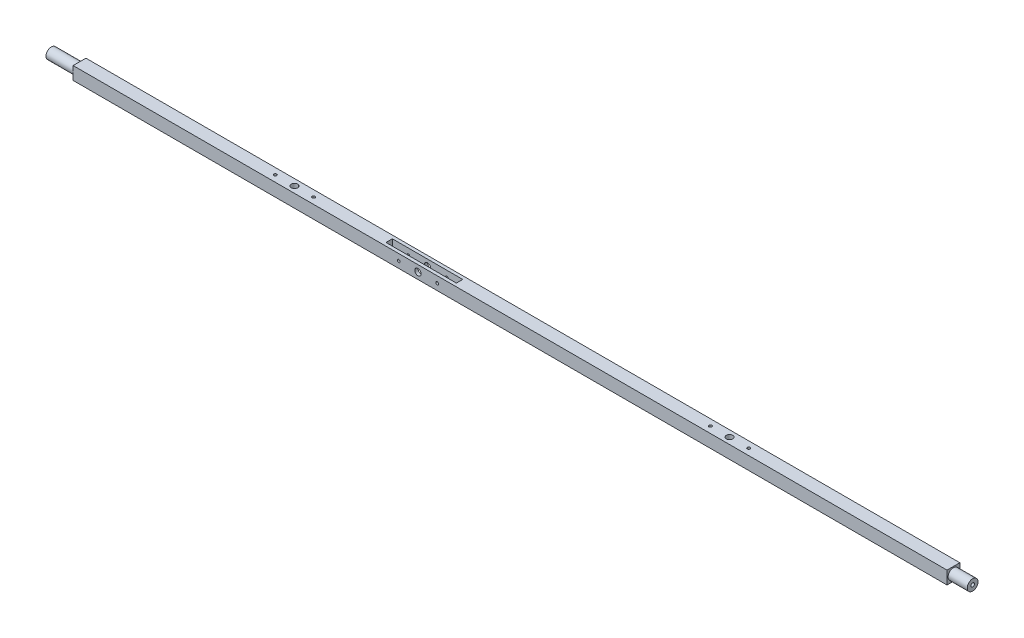
SolidWorks part; units mm, degrees
material "6061-T6 (SS)"
ref_plane "Front Plane" through (0, 0, 0) normal (0, 0, 1) x (1, 0, 0)
ref_plane "Top Plane" through (0, 0, 0) normal (0, 1, 0) x (1, 0, 0)
ref_plane "Right Plane" through (0, 0, 0) normal (1, 0, 0) x (0, 0, -1)
sketch "Sketch1" plane through (0, 0, 0) normal (1, 0, 0) x (0, 0, -1)
  line L1 (-6.35, -6.4107) -> (6.35, -6.4107)
  line L2 (-6.35, -6.4107) -> (-6.35, 6.4107)
  line L3 (-6.35, 6.4107) -> (6.35, 6.4107)
  line L4 (6.35, -6.4107) -> (6.35, 6.4107)
  line L5 (-6.35, -6.4107) -> (6.35, 6.4107) construction
  line L6 (-6.35, 6.4107) -> (6.35, -6.4107) construction
  point P0 (0, 0)
  dimension "D1" = 12.7
  dimension "D2" = 12.8213
extrude "Length" add sketch "Sketch1" along normal mid plane 914.4
ref_plane "Top" through (457.2, 0, 0) normal (1, 0, 0) x (0, 0, -1)
sketch "Sketch2" plane through (457.2, 0, 0) normal (1, 0, 0) x (0, 0, -1)
  line L5 (-3.7537, -3.7896) -> (2.2344, 2.2557) construction
  line L6 (-3.7537, 3.7896) -> (3.7537, -3.7896) construction
  line L7 (-6.35, -6.4107) -> (6.35, -6.4107)
  line L8 (-6.35, -6.4107) -> (-6.35, 6.4107)
  line L9 (-6.35, 6.4107) -> (6.35, 6.4107)
  line L10 (6.35, -6.4107) -> (6.35, 6.4107)
  line L11 (-6.35, -6.4107) -> (6.35, 6.4107) construction
  line L12 (-6.35, 6.4107) -> (6.35, -6.4107) construction
  circle A0 centre (0, 0) radius 5.334
  point P0 (0, 0)
  dimension "D1" = 10.668
extrude "Round Cut 1" cut sketch "Sketch2" against normal blind 19.05 contours L7 L10 L9 L8 A0 region at (457.2, 0, 6.1695)
ref_plane "Bottom Plane" through (-457.2, 0, 0) normal (-1, 0, 0) x (0, 0, 1)
sketch "Sketch3" plane through (-457.2, 0, 0) normal (-1, 0, 0) x (0, 0, 1)
  line L1 (-6.35, -6.4107) -> (6.35, -6.4107)
  line L2 (-6.35, -6.4107) -> (-6.35, 6.4107)
  line L3 (-6.35, 6.4107) -> (6.35, 6.4107)
  line L4 (6.35, -6.4107) -> (6.35, 6.4107)
  line L5 (-6.35, -6.4107) -> (6.35, 6.4107) construction
  line L6 (-6.35, 6.4107) -> (6.35, -6.4107) construction
  circle A0 centre (0, 0) radius 5.334
  point P0 (0, 0)
  dimension "D1" = 10.668
extrude "Round Cut 2" cut sketch "Sketch3" against normal blind 27.94 contours L1 L4 L3 L2 A0 | L2 L1 L4 L3 | A0 region at (-457.2, 0, -6.1695)
ref_plane "Plane13" through (0, -6.4107, 0) normal (0, -1, 0) x (-1, 0, 0)
sketch "Sketch9" plane through (0, -6.4107, 0) normal (0, -1, 0) x (-1, 0, 0)
  line L0 (-438.15, 6.35) -> (429.26, 6.35) construction
  line L1 (-330.2, 6.35) -> (-279.4, 6.35)
  line L2 (-330.2, 6.35) -> (-330.2, -6.35)
  line L3 (-330.2, -6.35) -> (-279.4, -6.35)
  line L4 (-279.4, 6.35) -> (-279.4, -6.35)
  line L5 (-438.15, -6.35) -> (429.26, -6.35) construction
  line L6 (-457.2, 6.985) -> (-457.2, -6.985) construction
  dimension "D1" = 50.8
  dimension "D2" = 127
sketch "Sketch10" plane through (0, -6.4107, 0) normal (0, -1, 0) x (-1, 0, 0)
  line L0 (457.2, -5.334) -> (457.2, 5.334) construction
  line L1 (101.6, -4.7642) -> (406.4, -4.7642)
  line L2 (101.6, -4.7642) -> (101.6, 4.6338)
  line L3 (101.6, 4.6338) -> (406.4, 4.6338)
  line L4 (406.4, -4.7642) -> (406.4, 4.6338)
  line L5 (101.6, -4.7642) -> (406.4, 4.6338) construction
  line L6 (101.6, 4.6338) -> (406.4, -4.7642) construction
  point P0 (254, -0.0652)
  dimension "D1" = 9.398
  dimension "D2" = 304.8
  dimension "D3" = 203.2
extrude "Cut-Extrude2" [suppressed] cut sketch "Sketch10" against normal blind 7.5438
ref_plane "Plane14" through (0, 0, 6.35) normal (0, 0, 1) x (1, 0, 0)
sketch "Sketch11" [suppressed] plane through (0, 0, 6.35) normal (0, 0, 1) x (1, 0, 0)
  line L0 (-50.8, 1.1331) -> (-355.6, 1.1331) construction
  line L1 (-355.6, 1.1331) -> (-355.6, -6.4107) construction
  line L2 (-349.25, -2.6769) -> (-63.4679, -2.6769) construction
  circle A0 centre (-349.25, -2.6769) radius 1.2573
  circle A1 centre (-336.55, -2.6769) radius 1.2573
  circle A2 centre (-323.85, -2.6769) radius 1.2573
  circle A3 centre (-311.15, -2.6769) radius 1.2573
  circle A4 centre (-298.45, -2.6769) radius 1.2573
  circle A5 centre (-285.75, -2.6769) radius 1.2573
  circle A6 centre (-273.05, -2.6769) radius 1.2573
  circle A7 centre (-260.35, -2.6769) radius 1.2573
  circle A8 centre (-247.65, -2.6769) radius 1.2573
  circle A9 centre (-234.95, -2.6769) radius 1.2573
  circle A10 centre (-222.25, -2.6769) radius 1.2573
  circle A11 centre (-209.55, -2.6769) radius 1.2573
  circle A12 centre (-196.85, -2.6769) radius 1.2573
  circle A13 centre (-184.15, -2.6769) radius 1.2573
  circle A14 centre (-171.45, -2.6769) radius 1.2573
  circle A15 centre (-158.75, -2.6769) radius 1.2573
  circle A16 centre (-146.05, -2.6769) radius 1.2573
  circle A17 centre (-133.35, -2.6769) radius 1.2573
  circle A18 centre (-120.65, -2.6769) radius 1.2573
  circle A19 centre (-107.95, -2.6769) radius 1.2573
  circle A20 centre (-95.25, -2.6769) radius 1.2573
  circle A21 centre (-82.55, -2.6769) radius 1.2573
  circle A22 centre (-69.85, -2.6769) radius 1.2573
  circle A23 centre (-57.15, -2.6769) radius 1.2573
  dimension "D1" = 2.5146
  dimension "D2" = 3.81
  dimension "D3" = 24
  dimension "25" = 6.35
extrude "Cut-Extrude3" [suppressed] cut sketch "Sketch11" against normal through all
sketch "Sketch12" plane through (0, -6.4107, 0) normal (0, -1, 0) x (-1, 0, 0)
  line L1 (0, 3.175) -> (-38.1, 3.175)
  line L2 (0, 3.175) -> (0, -3.175)
  line L3 (0, -3.175) -> (-38.1, -3.175)
  line L4 (-38.1, 3.175) -> (-38.1, -3.175)
  dimension "D1" = 38.1
  dimension "D2" = 6.35
  dimension "D3" = 3.175
  dimension "D4" = 0
extrude "Cut-Extrude4" [suppressed] cut sketch "Sketch12" against normal blind 6.35
sketch "Sketch13" [suppressed] plane through (0, 0, 6.35) normal (0, 0, 1) x (1, 0, 0)
  line L0 (0, -0.0607) -> (0, -6.4107) construction
  line L1 (378.46, -6.4107) -> (-378.46, -6.4107) construction
  circle A0 centre (5.08, -3.2357) radius 1.2573
  circle A1 centre (13.97, -3.2357) radius 1.2573
  circle A2 centre (22.86, -3.2357) radius 1.2573
  circle A3 centre (31.75, -3.2357) radius 1.2573
  dimension "D1" = 2.5146
  dimension "D3" = 5.08
  dimension "D4" = 3.175
  dimension "D2" = 4
extrude "Cut-Extrude5" [suppressed] cut sketch "Sketch13" against normal through all
sketch "Sketch14" plane through (457.2, 0, 0) normal (1, 0, 0) x (0, 0, -1)
  circle A0 centre (0, 0) radius 1.7526
  dimension "D1" = 3.5052
extrude "Cut-Extrude6" cut sketch "Sketch14" against normal blind 12.7
sketch "Sketch15" plane through (-457.2, 0, 0) normal (-1, 0, 0) x (0, 0, 1)
  circle A0 centre (0, 0) radius 1.7526
  dimension "D1" = 3.5052
extrude "Cut-Extrude7" cut sketch "Sketch15" against normal blind 19.05
ref_plane "Plane15" through (0, 6.4107, 0) normal (0, 1, 0) x (1, 0, 0)
sketch "Bottom Washer" plane through (0, 6.4107, 0) normal (0, 1, 0) x (1, 0, 0)
  line L1 (-457.2, 5.334) -> (-457.2, -5.334) construction
  circle A1 centre (-196.85, 0) radius 1.4224
  circle A2 centre (-234.95, 0) radius 1.4224
  point P2 (-457.2, 1.3557)
  dimension "D4" = 2.8448
  dimension "D5" = 2.8448
  dimension "D1" = 222.25
  dimension "D2" = 38.1
extrude "Bottom washer bolts" cut sketch "Bottom Washer" against normal blind 10.922 contours A1 | A2 region at (-196.85, 6.4107, 0) region at (-234.95, 6.4107, 0)
sketch "Sketch18" plane through (0, 6.4107, 0) normal (0, 1, 0) x (1, 0, 0)
  line L0 (-457.2, 5.334) -> (-457.2, -5.334) construction
  circle A0 centre (-215.9, 0) radius 3.175
  dimension "D1" = 6.35
  dimension "D2" = 241.3
extrude "Bottom Washer Center Bolt" cut sketch "Sketch18" against normal up to next
sketch "Sketch17" plane through (0, 6.4107, 0) normal (0, 1, 0) x (1, 0, 0)
  line L0 (457.2, -5.334) -> (457.2, 5.334) construction
  circle A0 centre (215.9, 0) radius 3.175
  dimension "D1" = 6.35
  dimension "D2" = 241.3
extrude "Top Washer Center Bolt" cut sketch "Sketch17" against normal up to next
sketch "Sketch16" plane through (0, 6.4107, 0) normal (0, 1, 0) x (1, 0, 0)
  line L0 (457.2, -5.334) -> (457.2, 5.334) construction
  circle A1 centre (234.95, 0) radius 1.4224
  circle A2 centre (196.85, 0) radius 1.4224
  dimension "D1" = 38.1
  dimension "D3" = 2.8448
  dimension "D4" = 2.8448
  dimension "D2" = 222.25
extrude "Top Washer" cut sketch "Sketch16" against normal blind 10.922
ref_plane "Plane16" through (0, -6.4107, 0) normal (0, -1, 0) x (-1, 0, 0)
sketch "Sketch19" plane through (0, -6.4107, 0) normal (0, -1, 0) x (-1, 0, 0)
  line L0 (-438.15, 6.35) -> (429.26, 6.35) construction
  line L1 (52.0606, 3.175) -> (121.9106, 3.175)
  line L2 (52.0606, 3.175) -> (52.0606, -3.175)
  line L3 (52.0606, -3.175) -> (121.9106, -3.175)
  line L4 (121.9106, 3.175) -> (121.9106, -3.175)
  line L5 (429.26, 6.35) -> (429.26, -6.35) construction
  dimension "D1" = 6.35
  dimension "D2" = 3.175
  dimension "D3" = 69.85
  dimension "D4" = 307.3494
extrude "Cut-Extrude8" cut sketch "Sketch19" against normal through all
ref_plane "Plane17" through (0, 0, 6.35) normal (0, 0, 1) x (1, 0, 0)
sketch "Sketch20" plane through (0, 0, 6.35) normal (0, 0, 1) x (1, 0, 0)
  line L0 (-86.9856, 6.4107) -> (-86.9856, -6.4107) construction
  line L1 (-52.0606, 6.4107) -> (-52.0606, -6.4107) construction
  line L3 (-121.9106, 0) -> (-52.0606, 0) construction
  line L6 (-121.9106, -6.4107) -> (-52.0606, -6.4107)
  line L7 (-121.9106, 6.4107) -> (-121.9106, -6.4107)
  line L8 (-52.0606, 6.4107) -> (-121.9106, 6.4107)
  line L9 (-52.0606, -6.4107) -> (-52.0606, 6.4107)
  line L10 (-121.9106, -6.4107) -> (-52.0606, -6.4107) construction
  line L11 (-121.9106, 6.4107) -> (-121.9106, -6.4107) construction
  line L12 (-52.0606, 6.4107) -> (-121.9106, 6.4107) construction
  line L13 (-52.0606, -6.4107) -> (-52.0606, 6.4107) construction
  circle A0 centre (-106.0356, 0) radius 1.397
  circle A1 centre (-86.9856, 0) radius 3.175
  circle A2 centre (-67.9356, 0) radius 1.397
  point P18 (0, 0)
  point P19 (0, 0)
  dimension "D1" = 2.794
  dimension "D2" = 6.35
  dimension "D3" = 2.794
  dimension "D4" = 15.875
  dimension "D5" = 19.05
  dimension "D6" = 19.05
  dimension "D7" = 0
extrude "Cut-Extrude9" cut sketch "Sketch20" against normal through all
equation "\"Diameter\"= .420"
equation "\"Round Cut Depth Top\"= .75"
equation "\"Stringer Length\"=36"
equation "\"D1@Sketch3\"= \"Diameter\""
equation "\"D1@Sketch2\"= \"Diameter\""
equation "\"D1@Round Cut 1\"= \"Round Cut Depth Top\""
equation "\"D1@Round Cut 2\" = \"Round Cut Depth Bottom\""
equation "\"D1@Length\"= \"Stringer Length\""
equation "\"Round Cut Depth Bottom\"= 1.1"
